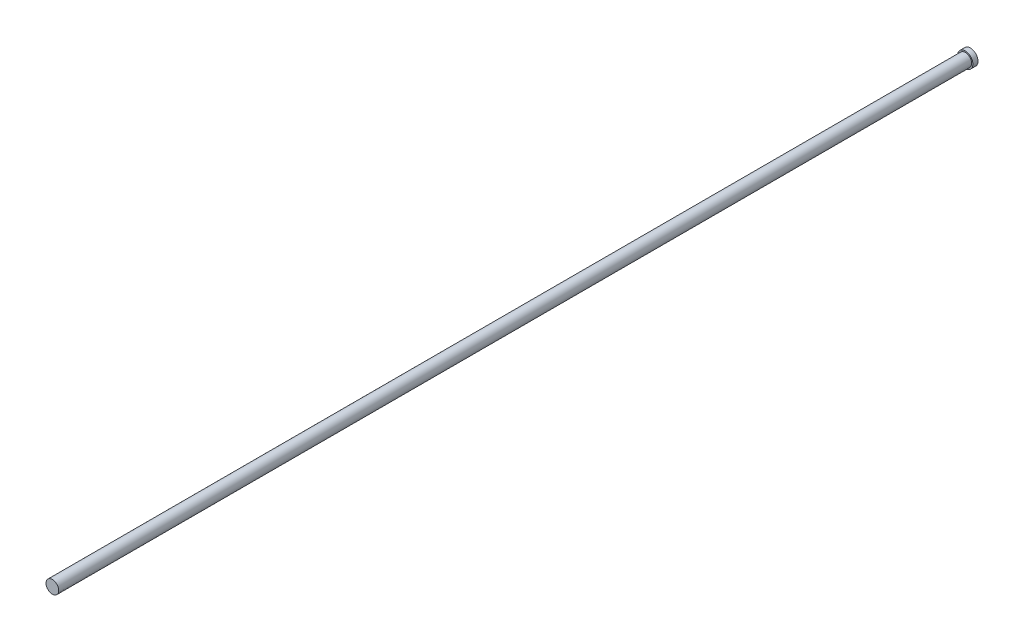
SolidWorks part; units mm, degrees
ref_plane "Front Plane" through (0, 0, 0) normal (0, 0, 1) x (1, 0, 0)
ref_plane "Top Plane" through (0, 0, 0) normal (0, 1, 0) x (1, 0, 0)
ref_plane "Right Plane" through (0, 0, 0) normal (1, 0, 0) x (0, 0, -1)
sketch "Sketch2" plane through (0, 0, 0) normal (0, 0, 1) x (1, 0, 0)
  circle A0 centre (-13.0879, 5.5684) radius 3
  circle A1 centre (-13.0869, 5.5492) radius 2.5
  dimension "D1" = 6
  dimension "D2" = 5
extrude "Boss-Extrude1" add sketch "Sketch2" along normal blind 358.39 contours A1
extrude "Boss-Extrude2" add sketch "Sketch2<5>" against normal blind 2 contours A0
sketch "Sketch2<5>" plane through (0, 0, 0) normal (0, 0, 1) x (1, 0, 0) same geometry as "Sketch2"
